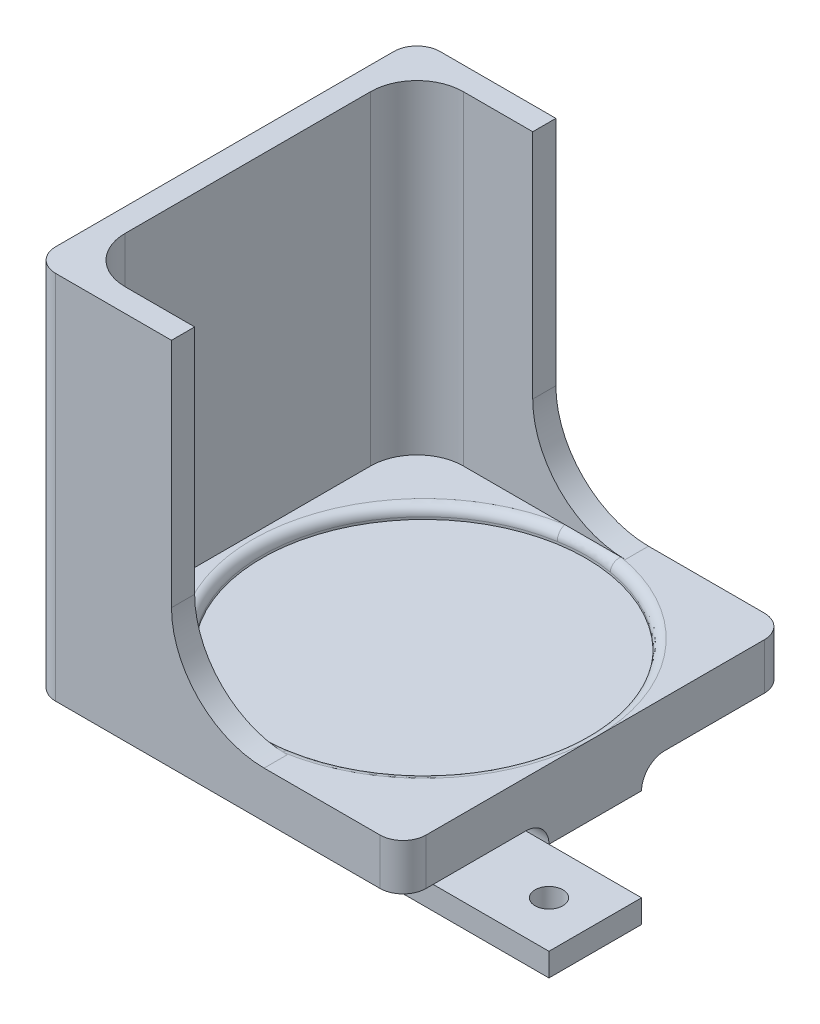
SolidWorks part; units mm, degrees
ref_plane "前基準面" through (0, 0, 0) normal (0, 0, 1) x (1, 0, 0)
ref_plane "上基準面" through (0, 0, 0) normal (0, 1, 0) x (1, 0, 0)
ref_plane "右基準面" through (0, 0, 0) normal (1, 0, 0) x (0, 0, -1)
sketch "草圖2" plane through (0, 0, 0) normal (0, 1, 0) x (1, 0, 0)
  line L1 (-35, 41.5) -> (35, 41.5)
  line L2 (-40, 36.5) -> (-40, -36.5)
  line L3 (-35, -41.5) -> (35, -41.5)
  line L4 (40, 36.5) -> (40, -36.5)
  line L5 (-40, 41.5) -> (40, -41.5) construction
  line L6 (-40, -41.5) -> (40, 41.5) construction
  arc A0 (35, 41.5) -> (40, 36.5) centre (35, 36.5) cw
  arc A1 (35, -41.5) -> (40, -36.5) centre (35, -36.5) ccw
  arc A2 (-40, -36.5) -> (-35, -41.5) centre (-35, -36.5) ccw
  arc A3 (-35, 41.5) -> (-40, 36.5) centre (-35, 36.5) ccw
  point P0 (0, 0)
  dimension "D3" = 5
  dimension "D1" = 80
  dimension "D2" = 83
extrude "填料-伸長1" add sketch "草圖2" along normal blind 10
sketch "草圖3" plane through (0, 10, 0) normal (0, 1, 0) x (1, 0, 0)
  line L0 (0, -45.9482) -> (0, 50.4274) construction
  line L1 (64.5067, 0) -> (-60.7671, 0) construction
  line L2 (-25, -36.5) -> (40, -36.5)
  line L4 (35, 41.5) -> (-35, 41.5) construction
  line L7 (35, 41.5) -> (-35, 41.5)
  line L8 (-40, 36.5) -> (-40, -36.5)
  line L9 (-35, -41.5) -> (35, -41.5)
  line L10 (40, -36.5) -> (40, 36.5)
  line L12 (-40, 36.5) -> (-40, -36.5)
  line L13 (-35, -41.5) -> (35, -41.5)
  line L15 (-35, -26.5) -> (-35, 26.5)
  line L18 (-25, 36.5) -> (40, 36.5)
  line L19 (35, 41.5) -> (-35, 41.5)
  arc A2 (-35, 41.5) -> (-40, 36.5) centre (-35, 36.5) ccw construction
  arc A3 (-35, 41.5) -> (-40, 36.5) centre (-35, 36.5) ccw
  arc A4 (-25, -36.5) -> (-35, -26.5) centre (-25, -26.5) cw
  circle A5 centre (0, 0) radius 35 construction
  arc A6 (40, 36.5) -> (35, 41.5) centre (35, 36.5) ccw
  arc A7 (-35, 41.5) -> (-40, 36.5) centre (-35, 36.5) ccw
  arc A8 (-40, -36.5) -> (-35, -41.5) centre (-35, -36.5) ccw
  arc A9 (35, -41.5) -> (40, -36.5) centre (35, -36.5) ccw
  arc A12 (-40, -36.5) -> (-35, -41.5) centre (-35, -36.5) ccw
  arc A13 (35, -41.5) -> (40, -36.5) centre (35, -36.5) ccw
  arc A18 (-25, 36.5) -> (-35, 26.5) centre (-25, 26.5) ccw
  arc A19 (35, 41.5) -> (40, 36.5) centre (35, 36.5) cw
  point P32 (0, 35)
  point P34 (-35, 0)
  point P42 (-35, 35)
  dimension "D1" = 10
  dimension "D3" = 70
  dimension "D2" = 0
extrude "填料-伸長2" add sketch "草圖3" along normal blind 70
sketch "草圖5" plane through (0, 10, 0) normal (0, 1, 0) x (1, 0, 0)
  line L0 (-49.8846, 0) -> (51.8846, 0) construction
  line L1 (3, 0) -> (51.8846, 0) construction
  line L4 (40, -36.5) -> (40, 36.5) construction
  circle A0 centre (3, 0) radius 35
  dimension "D1" = 70
  dimension "D2" = 37
extrude "除料-伸長3" cut sketch "草圖5" against normal blind 2.5
sketch "草圖6" plane through (0, 0, 0) normal (0, -1, 0) x (1, 0, 0)
  line L7 (-40, -36.5) -> (-40, 36.5) construction
  line L8 (40, 10) -> (-40, 10)
  line L9 (40, 10) -> (40, -10)
  line L10 (40, -10) -> (-40, -10)
  line L11 (-40, 10) -> (-40, -10)
  line L12 (40, 10) -> (-40, -10) construction
  line L13 (40, -10) -> (-40, 10) construction
  point P0 (0, 0)
  point P8 (0, 0)
  dimension "D1" = 20
  dimension "D2" = 80
extrude "填料-伸長3" add sketch "草圖6" along normal blind 30
sketch "草圖7" plane through (0, 0, 36.5) normal (0, 0, -1) x (-1, 0, 0)
  line L1 (-35, 80) -> (35, 80) construction
  line L2 (10, 80) -> (-40, 80)
  line L3 (-40, 80) -> (-40, 10)
  line L4 (40, 80) -> (40, 0) construction
  line L6 (-40, 80) -> (-40, 10) construction
  line L7 (40, -30) -> (-40, -30) construction
  line L8 (10, 80) -> (10, 30)
  line L9 (-10, 10) -> (-40, 10)
  arc A0 (10, 30) -> (-10, 10) centre (-10, 30) cw
  dimension "D3" = 20
  dimension "D1" = 30
  dimension "D2" = 40
extrude "除料-伸長4" cut sketch "草圖7" against normal through all and the other way through all
fillet "圓角1" radius 2 1 edges at (3, 10, 35)
sketch "草圖8" plane through (0, -30, 0) normal (0, -1, 0) x (1, 0, 0)
  line L0 (-50.5753, 0) -> (52.502, 0) construction
  line L1 (40, -10) -> (40, 10) construction
  circle A0 centre (30, 0) radius 3
  dimension "D1" = 6
  dimension "D2" = 10
extrude "除料-伸長5" cut sketch "草圖8" against normal blind 15
fillet "圓角2" radius 5 2 edges at (0, 0, 10) (0, 0, -10)
sketch "草圖9" plane through (40, 0, 0) normal (1, 0, 0) x (0, 0, -1)
  line L0 (-15, 0) -> (15, 0) construction
  line L2 (-10, -30) -> (-10, -5) construction
  line L3 (-10, -5) -> (10, -5)
  line L4 (10, -30) -> (10, -5) construction
  line L11 (-10, -25) -> (10, -25)
  line L13 (10, -30) -> (-10, -30) construction
  line L14 (-10, -5) -> (-10, -25)
  line L15 (10, -25) -> (10, -5)
  arc A0 (-10, -5) -> (-15, 0) centre (-15, -5) ccw construction
  arc A1 (15, 0) -> (10, -5) centre (15, -5) ccw construction
  arc A2 (-10, -5) -> (-15, 0) centre (-15, -5) ccw construction
  arc A3 (15, 0) -> (10, -5) centre (15, -5) ccw construction
  line M7 (-10, -5) -> (-10, -30)
  line M9 (10, -30) -> (10, -5)
  dimension "D1" = 5
  dimension "D2" = 5
extrude "除料-伸長6" cut sketch "草圖9" against normal blind 30 contours L11 M7 M9 region at (40, -15, 0)
fillet "圓角4" radius 2 2 edges at (10, -25, 0) (10, -5, 0)
